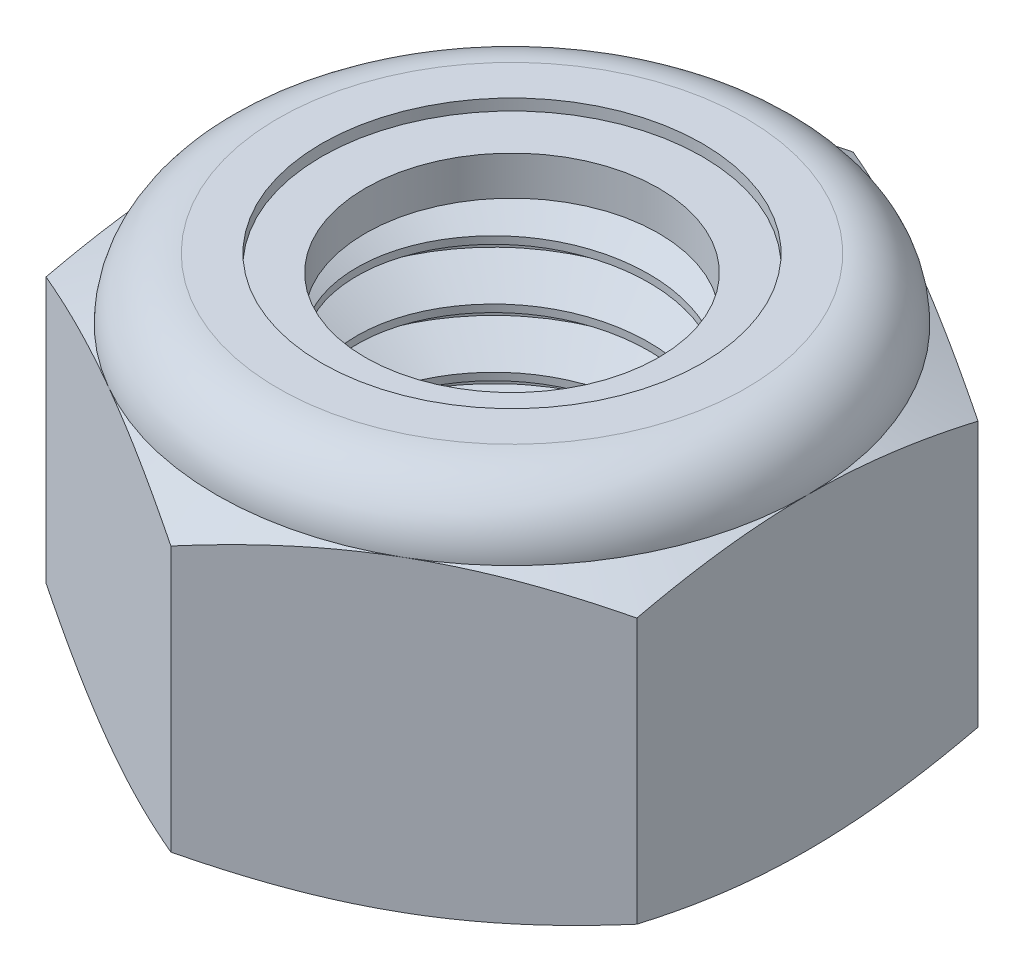
SolidWorks part; units mm, degrees
ref_plane "Front" through (0, 0, 0) normal (0, 0, 1) x (1, 0, 0)
ref_plane "Top" through (0, 0, 0) normal (0, 1, 0) x (1, 0, 0)
ref_plane "Right" through (0, 0, 0) normal (1, 0, 0) x (0, 0, -1)
sketch "Sketch1" plane through (0, 0, 0) normal (0, 1, 0) x (1, 0, 0)
  line L0 (0, 0) -> (1.7678, -1.7678) construction
  line L1 (0, 4.6188) -> (-4, 2.3094)
  line L2 (-4, 2.3094) -> (-4, -2.3094)
  line L3 (-4, -2.3094) -> (0, -4.6188)
  line L4 (0, -4.6188) -> (4, -2.3094)
  line L5 (4, -2.3094) -> (4, 2.3094)
  line L6 (4, 2.3094) -> (0, 4.6188)
  circle A0 centre (0, 0) radius 4 construction
  circle A1 centre (0, 0) radius 2.5
  point P12 (1.7678, -1.7678)
  dimension "Thread Dia" = 5
  dimension "Hex Flats" = 8
  dimension "D1" = 45
extrude "Extrude1" add sketch "Sketch1" along normal blind 5
chamfer "Chamfer1" distance 0.25 angle 45 1 edges at (0, 0, 2.5)
sketch "Sketch5" plane through (0, 0, 0) normal (1, 0, 0) x (0, 0, -1)
  line L0 (0, 0) -> (4, 0)
  line L1 (4, 0) -> (4.6188, 0.2886)
  line L2 (4.6188, 0.2886) -> (4.6188, 3.8781)
  line L3 (4.6188, 3.8781) -> (4, 4.1667)
  line L4 (3.1667, 5) -> (3.1667, 6.27)
  line L5 (3.1667, 6.27) -> (5.8888, 6.27)
  line L6 (5.8888, 6.27) -> (5.8888, -1.27)
  line L7 (5.8888, -1.27) -> (0, -1.27)
  line L8 (0, -1.27) -> (0, 0)
  line L9 (4, 4.1667) -> (4, 0) construction
  line L10 (2.3094, 5) -> (4.6188, 5) construction
  line L13 (4.6188, 2.0833) -> (5.8888, 2.0833) construction
  line L14 (4.6188, 5) -> (4.6188, 0) construction
  line L15 (0, 0) -> (0, 6.27) construction
  line L20 (0, 6.27) -> (3.1667, 6.27) construction
  arc A0 (4, 4.1667) -> (3.1667, 5) centre (3.1667, 4.1667) ccw
  dimension "D1" = 25
  dimension "D2" = 1.27
  dimension "D3" = 5
  dimension "D4" = 0.8333
revolve "Cut-Revolve3" cut sketch "Sketch5" angle 360 about L15
sketch "Sketch6" plane through (0, 0, 0) normal (1, 0, 0) x (0, 0, -1)
  line L0 (0, 4.1667) -> (3.8476, 4.1667)
  line L1 (3.1667, 4.8476) -> (2.5762, 4.8476)
  line L2 (0, 6.27) -> (0, 4.1667)
  line L3 (2.5762, 6.27) -> (0, 6.27)
  line L4 (0, 6.27) -> (3.1667, 6.27) construction
  line L5 (0, 0) -> (0, 6.27) construction
  line L6 (0, 6.27) -> (0, 0) construction
  line L7 (2.5762, 4.8476) -> (2.5762, 6.27)
  line L8 (3.1667, 5) -> (3.1667, 4.8476) construction
  line L9 (2.5762, 4.8476) -> (2.4238, 4.8476) construction
  line L21 (2.5, 4.8476) -> (2.5, 5) construction
  arc A0 (3.8476, 4.1667) -> (3.1667, 4.8476) centre (3.1667, 4.1667) ccw
  arc A1 (4, 4.1667) -> (3.1667, 5) centre (3.1667, 4.1667) ccw construction
  dimension "D1" = 0.1524
revolve "Cut-Revolve4" cut sketch "Sketch6" angle 360 about L6
sketch "Sketch7" plane through (0, 0, 0) normal (1, 0, 0) x (0, 0, -1)
  line L0 (1.9857, 4.2429) -> (3.7666, 4.2429)
  line L1 (3.1667, 4.7714) -> (1.9857, 4.7714)
  line L2 (1.9857, 4.7714) -> (1.9857, 4.2429)
  line L3 (1.9857, 4.2429) -> (0, 4.2429) construction
  line L4 (0, 4.2429) -> (0, 4.7714) construction
  line L5 (0, 4.7714) -> (1.9857, 4.7714) construction
  line L6 (1.9857, 4.2429) -> (1.9857, 4.1667) construction
  line L7 (0, 4.1667) -> (3.8476, 4.1667) construction
  line L8 (3.1667, 4.7714) -> (3.1667, 4.8476) construction
  line L10 (1.9857, 4.8476) -> (2.5762, 4.8476) construction
  line L11 (3.1667, 4.8476) -> (2.5762, 4.8476) construction
  arc A0 (3.7666, 4.2429) -> (3.1667, 4.7714) centre (3.1667, 4.1667) ccw
  arc A2 (3.8476, 4.1667) -> (3.1667, 4.8476) centre (3.1667, 4.1667) ccw construction
  dimension "D1" = 0.0762
revolve "Revolve2" add sketch "Sketch7" angle 360 about L4
ref_axis "Center Axis 1" through (0, 4.1667, 0) along (0, -1, 0)
sketch "Sketch12" plane through (0, 0, 0) normal (0, -1, 0) x (1, 0, 0)
  circle A0 centre (0, 0) radius 2.5
  circle A1 centre (0, 0) radius 2.5 construction
extrude "Boss-Extrude3" add sketch "Sketch12" against normal up to vertex (4.1667 mm away) up to point (0, 4.1667, -3.8476)
sketch "Sketch2" plane through (0, 0, 0) normal (1, 0, 0) x (0, 0, -1)
  line L1 (0, 0) -> (2.5, 0)
  line L2 (0, 0) -> (0, 4.8476)
  line L3 (0, 4.8476) -> (2.5, 4.8476)
  line L4 (2.5, 0) -> (2.5, 4.8476)
  line L7 (0, -2.5) -> (0, 0) construction
  line L11 (3.1667, 4.8476) -> (2.5762, 4.8476) construction
revolve "Revolve1" add sketch "Sketch2" angle 360 about L7
sketch "Sketch8" plane through (0, 0, 0) normal (0, -1, 0) x (1, 0, 0)
  circle A0 centre (0, 0) radius 2.5 construction
  circle A2 centre (0, 0) radius 2.5
curve "Helix/Spiral1" pitch 0.8 height 10 radius 2.5 centre (0, 0, 0) axis (0, 1, 0) start towards (0, 0, -1) parameters "Pitch"=0.8
sketch "Sketch9" plane through (0, 0, 0) normal (1, 0, 0) x (0, 0, -1)
  line L0 (2.5, -0.7) -> (2.5, 0)
  line L1 (2.5, -0.7) -> (1.9804, -0.4)
  line L2 (1.9804, -0.4) -> (1.9804, -0.3)
  line L3 (1.9804, -0.3) -> (2.5, 0)
  line L4 (-2.5, 0) -> (2.5, 0) construction
  line L5 (2.5, -0.35) -> (1.9804, -0.35) construction
  line L6 (2.2402, -0.55) -> (2.2402, -0.15) construction
  dimension "D1" = 0.1
  dimension "D2" = 0.4
  dimension "D3" = 60
sweep "Cut-Sweep1" cut profiles "Sketch9" path "Helix/Spiral1" align with end faces yes
combine bodies "Combine1" operation type subtract main body 135 bodies to subtract 132
sketch "Sketch14" plane through (0, 0, 0) normal (1, 0, 0) x (0, 0, -1)
  line L0 (0, 0) -> (0, 5) construction
  line L1 (2.5762, 5) -> (-2.5762, 5) construction
  line L2 (-2.75, 0) -> (-1.25, 1.5)
  line L4 (-2.5, 0) -> (-2.75, 0)
  line L9 (-1.25, 1.5) -> (0, 1.5)
  line L10 (0, 1.5) -> (0, 0)
  line L11 (0, 0) -> (-2.5, 0)
  line L12 (-1.25, 1.5) -> (-1.25, 0) construction
  dimension "D1" = 45
  dimension "D2" = 5
  dimension "D3" = 0.25
revolve "Cut-Revolve5" cut sketch "Sketch14" angle 360 about L0
equation "\"D4@Sketch5\"=\"Height@Extrude1\"/6"
equation "\"D3@Helix/Spiral1\"=2*\"Height@Extrude1\""
equation "\"D1@Sketch9\"=\"Pitch@Helix/Spiral1\"*.125"
equation "\"D2@Sketch9\"=\"Pitch@Helix/Spiral1\"*.50"
equation "\"D1@Chamfer1\"=.05*\"Thread Dia@Sketch1\""
equation "\"D2@Sketch14\"=\"Thread Dia@Sketch1\""
equation "\"D3@Sketch14\"=\"D1@Chamfer1\""
